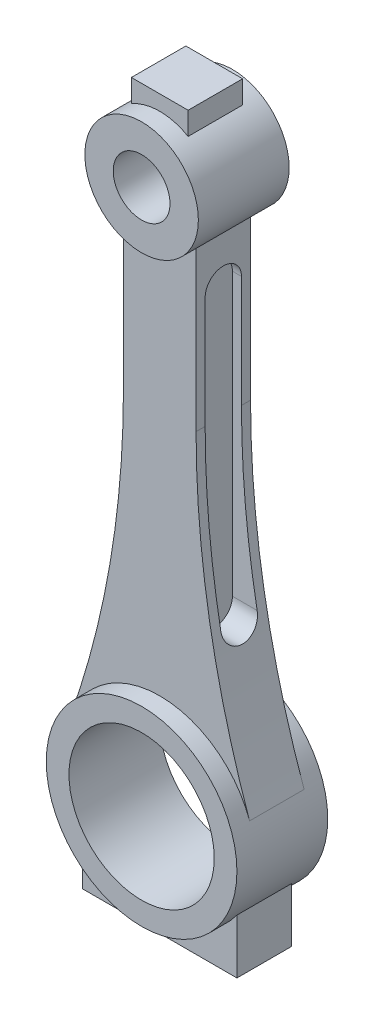
SolidWorks part; units mm, degrees
ref_plane "Front Plane" through (0, 0, 0) normal (0, 0, 1) x (1, 0, 0)
ref_plane "Top Plane" through (0, 0, 0) normal (0, 1, 0) x (1, 0, 0)
ref_plane "Right Plane" through (0, 0, 0) normal (1, 0, 0) x (0, 0, -1)
sketch "Sketch1" plane through (0, 0, 0) normal (0, 0, 1) x (1, 0, 0)
  line L0 (0, 0) -> (0, 174.1083) construction
  line L1 (-8, 75.3953) -> (-8, 110.3953)
  line L2 (8, 75.3953) -> (8, 110.3953)
  line L3 (-6.25, 135.8253) -> (6.25, 135.8253)
  line L4 (6.25, 135.8253) -> (6.25, 130.8253)
  line L5 (-6.25, 135.8253) -> (-6.25, 130.8253)
  line L6 (0, 0) -> (0, -39.4731) construction
  line L7 (-17, -24.3288) -> (17, -24.3288)
  line L8 (17, -24.3288) -> (17, -12.3288)
  line L9 (-17, -24.3288) -> (-17, -12.3288)
  circle A0 centre (0, 0) radius 21
  circle A1 centre (0, 0) radius 16
  circle A2 centre (0, 120) radius 12.5
  circle A3 centre (0, 120) radius 6.25
  arc A4 (-8, 75.3953) -> (-19.7874, 7.0327) centre (-212.1328, 75.3953) cw
  arc A5 (8, 75.3953) -> (19.7874, 7.0327) centre (212.1328, 75.3953) ccw
  point P25 (0, 0)
  point P26 (0, 0)
  dimension "D2" = 42
  dimension "D3" = 32
  dimension "D4" = 25
  dimension "D5" = 12.5
  dimension "D1" = 120
  dimension "D6" = 8
  dimension "D7" = 35
  dimension "D8" = 12.5
  dimension "D9" = 5
  dimension "D10" = 5
  dimension "D11" = 34
  dimension "D12" = 12
  dimension "D13" = 12
extrude "Boss-Extrude1" add sketch "Sketch1" along normal mid plane 20 contours A2 | A0 | A1 | A3
extrude "Boss-Extrude3" add sketch "Sketch1<4>" along normal mid plane 12 contours A5 L2 A2 L1 A4 A0 | A2 L4 L3 L5 | A0 L9 L7 L8 region at (0, 57.8448, 0) region at (0, 133.8599, 0) region at (0, -21.3606, 0)
sketch "Sketch1<4>" plane through (0, 0, 0) normal (0, 0, 1) x (1, 0, 0) same geometry as "Sketch1"
sketch "Sketch3" plane through (0, 0, 0) normal (1, 0, 0) x (0, 0, -1)
  line L0 (-10, 120) -> (10, 120) construction
  line L1 (-10, 132.5) -> (-10, 107.5) construction
  line L2 (10, 107.5) -> (10, 132.5) construction
  line L3 (0, 100) -> (0, 38) construction
  line L4 (0, 75.3953) -> (0, 110.3953) construction
  line L5 (0, 75.3953) -> (0, 7.0327) construction
  line L6 (4, 100) -> (4, 38)
  line L7 (-4, 100) -> (-4, 38)
  arc A0 (4, 100) -> (-4, 100) centre (0, 100) ccw
  arc A1 (-4, 38) -> (4, 38) centre (0, 38) ccw
  point P12 (0, 69)
  dimension "D3" = 4
  dimension "D1" = 62
  dimension "D2" = 20
extrude "Cut-Extrude1" cut sketch "Sketch3" against normal through all from offset 6 offset against normal yes
mirror "Mirror1" about plane through (0, 0, 0) normal (1, 0, 0) of "Cut-Extrude1"
